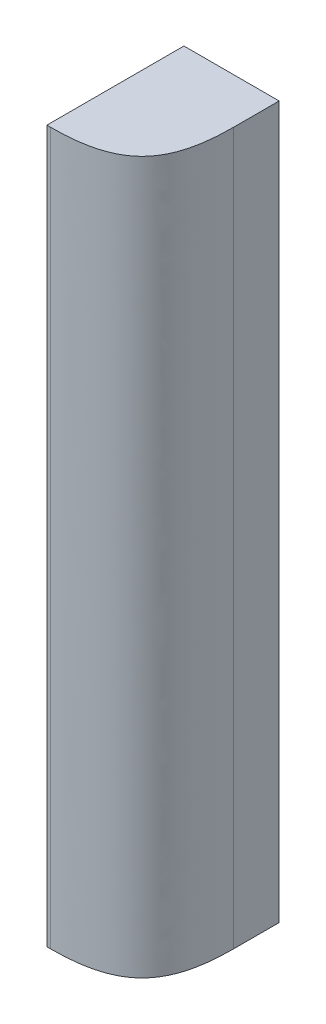
SolidWorks part; units mm, degrees
ref_plane "Front Plane" through (0, 0, 0) normal (0, 0, 1) x (1, 0, 0)
ref_plane "Top Plane" through (0, 0, 0) normal (0, 1, 0) x (1, 0, 0)
ref_plane "Right Plane" through (0, 0, 0) normal (1, 0, 0) x (0, 0, -1)
sketch "Sketch1" plane through (0, 0, 0) normal (0, 1, 0) x (1, 0, 0)
  line L1 (0, 0) -> (25, 0)
  line L2 (0, 0) -> (0, 36)
  line L3 (0, 36) -> (25, 36)
  line L4 (25, 0) -> (25, 36)
  dimension "D1" = 36
  dimension "D2" = 25
extrude "Boss-Extrude1" add sketch "Sketch1" along normal blind 186.9
fillet "Fillet1" radius 24 1 edges at (25, 93.45, 0) conic rho 0.55
